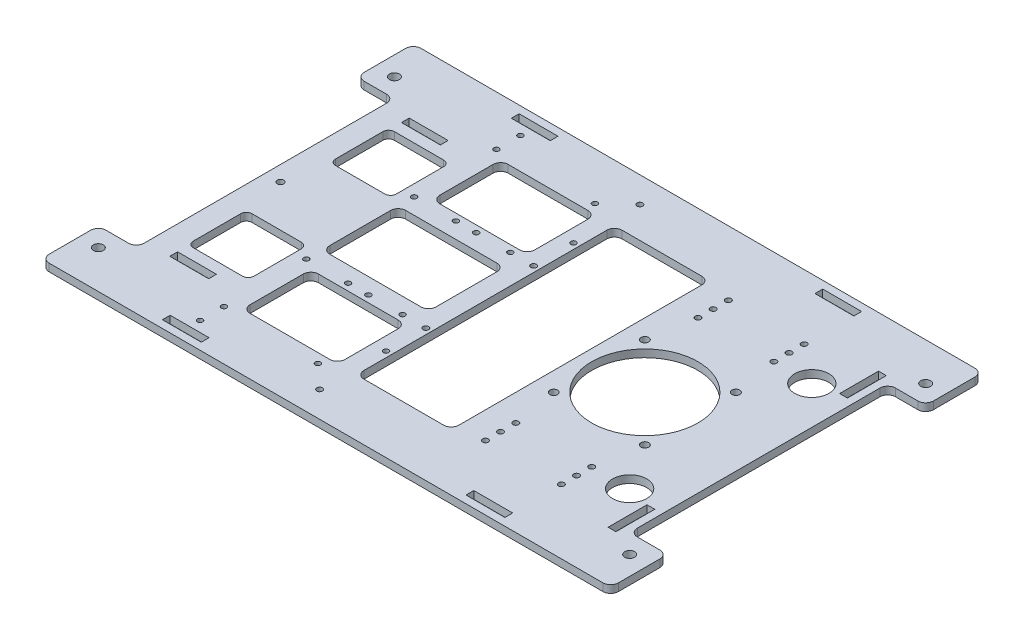
SolidWorks part; units mm, degrees
material "Ст 3 ГОСТ 380-88"
ref_plane "Спереди" through (0, 0, 0) normal (0, 0, 1) x (1, 0, 0)
ref_plane "Сверху" through (0, 0, 0) normal (0, 1, 0) x (1, 0, 0)
ref_plane "Справа" through (0, 0, 0) normal (1, 0, 0) x (0, 0, -1)
other "Configuration Table"
sketch "Эскиз1" plane through (0, 0, 0) normal (0, 1, 0) x (1, 0, 0)
  line L0 (0, -170.1085) -> (0, -191.8915)
  line L1 (4.1085, 0) -> (295.8915, 0)
  line L2 (0, -4.1085) -> (0, -25.8915)
  line L3 (4.1085, -196) -> (295.8915, -196)
  line L4 (300, -4.1085) -> (300, -25.8915)
  line L5 (4.1085, -30) -> (15.8915, -30)
  line L7 (4.1085, -166) -> (15.8915, -166)
  line L8 (20, -34.1085) -> (20, -161.8915)
  line L9 (295.8915, -30) -> (284.1085, -30)
  line L11 (295.8915, -166) -> (284.1085, -166)
  line L12 (280, -34.1085) -> (280, -161.8915)
  line L13 (300, -170.1085) -> (300, -191.8915)
  line L14 (-22.5077, -98) -> (393.8408, -98) construction
  circle A0 centre (220, -98) radius 28
  arc A1 (295.8915, -30) -> (300, -25.8915) centre (295.8915, -25.8915) ccw
  arc A2 (295.8915, 0) -> (300, -4.1085) centre (295.8915, -4.1085) cw
  arc A3 (284.1085, -30) -> (280, -34.1085) centre (284.1085, -34.1085) ccw
  arc A4 (284.1085, -166) -> (280, -161.8915) centre (284.1085, -161.8915) cw
  arc A5 (300, -170.1085) -> (295.8915, -166) centre (295.8915, -170.1085) ccw
  arc A6 (295.8915, -196) -> (300, -191.8915) centre (295.8915, -191.8915) ccw
  arc A7 (0, -191.8915) -> (4.1085, -196) centre (4.1085, -191.8915) ccw
  arc A8 (0, -170.1085) -> (4.1085, -166) centre (4.1085, -170.1085) cw
  arc A9 (15.8915, -166) -> (20, -161.8915) centre (15.8915, -161.8915) ccw
  arc A10 (15.8915, -30) -> (20, -34.1085) centre (15.8915, -34.1085) cw
  arc A11 (4.1085, -30) -> (0, -25.8915) centre (4.1085, -25.8915) cw
  arc A12 (4.1085, 0) -> (0, -4.1085) centre (4.1085, -4.1085) ccw
  circle A13 centre (10, -20) radius 2.6
  circle A14 centre (290, -20) radius 2.6
  circle A15 centre (290, -176) radius 2.6
  circle A16 centre (10, -176) radius 2.6
  point P19 (300, -30)
  point P22 (300, 0)
  point P25 (280, -30)
  point P34 (0, -196)
  point P41 (20, -30)
  point P44 (0, -30)
  point P47 (0, 0)
  dimension "D8" = 56
  dimension "D10" = 4.1085
  dimension "D11" = 5.2
  dimension "D12" = 5.2
  dimension "D1" = 300
  dimension "D2" = 196
  dimension "D3" = 20
  dimension "D4" = 30
  dimension "D5" = 30
  dimension "D6" = 20
  dimension "D7" = 98
  dimension "D9" = 60
  dimension "D13" = 10
  dimension "D14" = 10
  dimension "D15" = 10
  dimension "D16" = 10
base flange "Базовая кромка1" sketch "Эскиз1" thickness 4 reverse thickness direction no parameters "D1"=4
sketch "Эскиз6" plane through (0, 0, 0) normal (0, 1, 0) x (1, 0, 0)
  line L0 (0, -98) -> (316.488, -98) construction
  line L1 (271.9, -26.75) -> (276, -26.75)
  line L2 (271.9, -26.75) -> (271.9, -47.25)
  line L3 (271.9, -47.25) -> (276, -47.25)
  line L4 (276, -26.75) -> (276, -47.25)
  line L5 (219.75, -4) -> (240.25, -4)
  line L6 (219.75, -4) -> (219.75, -8.1)
  line L7 (219.75, -8.1) -> (240.25, -8.1)
  line L8 (240.25, -4) -> (240.25, -8.1)
  line L9 (59.75, -4) -> (80.25, -4)
  line L10 (59.75, -4) -> (59.75, -8.1)
  line L11 (59.75, -8.1) -> (80.25, -8.1)
  line L12 (80.25, -4) -> (80.25, -8.1)
  line L21 (295.8915, 0) -> (4.1085, 0) construction
  line L22 (280, -161.8915) -> (280, -34.1085) construction
  line L23 (20, -34.1085) -> (20, -161.8915) construction
  line L24 (32.75, -34.9) -> (53.25, -34.9)
  line L25 (32.75, -34.9) -> (32.75, -39)
  line L26 (32.75, -39) -> (53.25, -39)
  line L27 (53.25, -34.9) -> (53.25, -39)
  line L28 (53.25, -161.1) -> (53.25, -157)
  line L29 (32.75, -157) -> (53.25, -157)
  line L30 (32.75, -161.1) -> (32.75, -157)
  line L31 (32.75, -161.1) -> (53.25, -161.1)
  line L32 (80.25, -192) -> (80.25, -187.9)
  line L33 (59.75, -187.9) -> (80.25, -187.9)
  line L34 (59.75, -192) -> (59.75, -187.9)
  line L35 (59.75, -192) -> (80.25, -192)
  line L36 (240.25, -192) -> (240.25, -187.9)
  line L37 (219.75, -187.9) -> (240.25, -187.9)
  line L38 (219.75, -192) -> (219.75, -187.9)
  line L39 (219.75, -192) -> (240.25, -192)
  line L40 (276, -169.25) -> (276, -148.75)
  line L41 (271.9, -148.75) -> (276, -148.75)
  line L42 (271.9, -169.25) -> (271.9, -148.75)
  line L43 (271.9, -169.25) -> (276, -169.25)
  dimension "D1" = 98
  dimension "D2" = 20.5
  dimension "D3" = 20.5
  dimension "D4" = 20.5
  dimension "D5" = 4.1
  dimension "D6" = 4
  dimension "D7" = 4
  dimension "D8" = 4
  dimension "D9" = 20.5
  dimension "D10" = 4.1
  dimension "D11" = 39.75
  dimension "D12" = 39.75
  dimension "D13" = 35
  dimension "D14" = 12.75
  dimension "D15" = 26.75
extrude "Вырез-Вытянуть1" cut sketch "Эскиз6" against normal up to next normal cut yes
sketch "Эскиз7" plane through (0, 0, 0) normal (0, 1, 0) x (1, 0, 0)
  line L0 (4.1085, 0) -> (295.8915, 0) construction
  line L1 (140, -30) -> (182, -30)
  line L2 (136, -34) -> (136, -162)
  line L3 (140, -166) -> (182, -166)
  line L4 (186, -34) -> (186, -162)
  line L5 (4.1085, -196) -> (295.8915, -196) construction
  line L6 (280, -34.1085) -> (280, -161.8915) construction
  line L7 (20, -34.1085) -> (20, -161.8915) construction
  line L8 (74, -78) -> (122, -78)
  line L9 (70, -82) -> (70, -114)
  line L10 (74, -118) -> (122, -118)
  line L11 (126, -82) -> (126, -114)
  line L12 (-22.5077, -98) -> (393.8408, -98) construction
  line L14 (32.75, -39) -> (53.25, -39) construction
  line L15 (35, -45) -> (61, -45)
  line L16 (32, -48) -> (32, -73)
  line L17 (35, -76) -> (61, -76)
  line L18 (64, -48) -> (64, -73)
  line L19 (20, -34.1085) -> (20, -161.8915) construction
  line L20 (220, -98) -> (-41.1636, -98) construction
  line L21 (64, -148) -> (64, -123)
  line L22 (35, -120) -> (61, -120)
  line L23 (32, -148) -> (32, -123)
  line L24 (35, -151) -> (61, -151)
  arc A0 (136, -162) -> (140, -166) centre (140, -162) ccw
  arc A1 (182, -166) -> (186, -162) centre (182, -162) ccw
  arc A2 (182, -30) -> (186, -34) centre (182, -34) cw
  arc A3 (140, -30) -> (136, -34) centre (140, -34) ccw
  arc A4 (122, -78) -> (126, -82) centre (122, -82) cw
  arc A5 (122, -118) -> (126, -114) centre (122, -114) ccw
  arc A6 (70, -114) -> (74, -118) centre (74, -114) ccw
  arc A7 (74, -78) -> (70, -82) centre (74, -82) ccw
  circle A8 centre (196, -74) radius 2.05
  circle A9 centre (220, -98) radius 28 construction
  circle A10 centre (244, -74) radius 2.05
  circle A11 centre (244, -122) radius 2.05
  circle A12 centre (196, -122) radius 2.05
  arc A13 (61, -76) -> (64, -73) centre (61, -73) ccw
  arc A14 (61, -45) -> (64, -48) centre (61, -48) cw
  arc A15 (35, -45) -> (32, -48) centre (35, -48) ccw
  arc A16 (32, -73) -> (35, -76) centre (35, -73) ccw
  arc A17 (32, -123) -> (35, -120) centre (35, -123) cw
  arc A18 (35, -151) -> (32, -148) centre (35, -148) cw
  arc A19 (61, -151) -> (64, -148) centre (61, -148) ccw
  arc A20 (61, -120) -> (64, -123) centre (61, -123) cw
  point P24 (186, -30)
  point P27 (136, -30)
  point P61 (64, -45)
  point P64 (32, -45)
  point P79 (32, -151)
  point P80 (64, -151)
  dimension "D9" = 4
  dimension "D12" = 4.1
  dimension "D18" = 3
  dimension "D1" = 30
  dimension "D2" = 30
  dimension "D3" = 94
  dimension "D4" = 50
  dimension "D5" = 50
  dimension "D6" = 40
  dimension "D7" = 20
  dimension "D8" = 10
  dimension "D10" = 24
  dimension "D11" = 24
  dimension "D14" = 22
  dimension "D15" = 6
  dimension "D16" = 12
  dimension "D17" = 32
  dimension "D13" = 2
extrude "Вырез-Вытянуть2" cut sketch "Эскиз7" against normal up to next normal cut yes
sketch "Эскиз14" plane through (0, 0, 0) normal (0, 1, 0) x (1, 0, 0)
  line L0 (295.8915, 0) -> (4.1085, 0) construction
  line L2 (0, -98) -> (328.8146, -98) construction
  line L5 (20, -34.1085) -> (20, -161.8915) construction
  line L6 (122, -78) -> (74, -78) construction
  line L7 (80, -30) -> (122, -30)
  line L8 (76, -34) -> (76, -62)
  line L9 (80, -66) -> (122, -66)
  line L10 (126, -34) -> (126, -62)
  line L11 (136, -34) -> (136, -162) construction
  line L12 (126, -162) -> (126, -134)
  line L13 (80, -130) -> (122, -130)
  line L14 (76, -162) -> (76, -134)
  line L15 (80, -166) -> (122, -166)
  circle A0 centre (70, -26.2) radius 1.4
  circle A1 centre (120.7, -25) radius 1.4
  circle A2 centre (70, -69.6) radius 1.4
  circle A3 centre (120.7, -69.6) radius 1.4
  circle A4 centre (70, -13.6) radius 1.4
  circle A5 centre (133, -13.6) radius 1.4947
  circle A6 centre (133, -69.6) radius 1.4762
  circle A7 centre (133, -126.4) radius 1.4762
  circle A8 centre (133, -182.4) radius 1.4947
  circle A9 centre (70, -182.4) radius 1.4
  circle A10 centre (120.7, -126.4) radius 1.4
  circle A11 centre (70, -126.4) radius 1.4
  circle A12 centre (120.7, -171) radius 1.4
  circle A13 centre (70, -169.8) radius 1.4
  arc A14 (122, -30) -> (126, -34) centre (122, -34) cw
  arc A15 (122, -66) -> (126, -62) centre (122, -62) ccw
  arc A16 (76, -62) -> (80, -66) centre (80, -62) ccw
  arc A17 (80, -30) -> (76, -34) centre (80, -34) ccw
  arc A18 (80, -166) -> (76, -162) centre (80, -162) cw
  arc A19 (76, -134) -> (80, -130) centre (80, -134) cw
  arc A20 (122, -130) -> (126, -134) centre (122, -134) cw
  arc A21 (122, -166) -> (126, -162) centre (122, -162) ccw
  circle A22 centre (133, -48.6) radius 1.4
  circle A23 centre (92, -69.6) radius 1.4
  circle A24 centre (61.7, -48.6) radius 1.4
  circle A25 centre (102.7, -69.6) radius 1.4
  circle A26 centre (102.7, -126.4) radius 1.4
  circle A27 centre (92, -126.4) radius 1.4
  circle A28 centre (133, -147.4) radius 1.4
  circle A29 centre (61.7, -147.4) radius 1.4
  circle A30 centre (28, -98) radius 1.75
  point P46 (126, -66)
  point P49 (76, -66)
  point P64 (76, -130)
  point P65 (126, -130)
  dimension "D2" = 2.8
  dimension "D14" = 4
  dimension "D21" = 3.5
  dimension "D1" = 50.7
  dimension "D3" = 43.4
  dimension "D4" = 44.6
  dimension "D5" = 25
  dimension "D6" = 50
  dimension "D7" = 98
  dimension "D8" = 56
  dimension "D9" = 63
  dimension "D10" = 50
  dimension "D11" = 30
  dimension "D12" = 12
  dimension "D13" = 10
  dimension "D15" = 21
  dimension "D16" = 41
  dimension "D17" = 21
  dimension "D18" = 41
  dimension "D19" = 18
  dimension "D20" = 8
extrude "Вырез-Вытянуть3" cut sketch "Эскиз14" against normal through all normal cut yes
sketch "Эскиз15" plane through (0, 0, 0) normal (0, 1, 0) x (1, 0, 0)
  line L0 (295.8915, 0) -> (4.1085, 0) construction
  line L1 (300, -25.8915) -> (300, -4.1085) construction
  line L2 (248, -98) -> (358.3996, -98) construction
  line L3 (280, -161.8915) -> (280, -34.1085) construction
  circle A0 centre (200, -34) radius 1.5
  circle A1 centre (240, -34) radius 1.5
  circle A2 centre (240, -42) radius 1.5
  circle A3 centre (240, -50) radius 1.5
  circle A4 centre (200, -42) radius 1.5
  circle A5 centre (200, -50) radius 1.5
  circle A6 centre (220, -98) radius 28 construction
  circle A7 centre (200, -146) radius 1.5
  circle A8 centre (200, -154) radius 1.5
  circle A9 centre (240, -146) radius 1.5
  circle A10 centre (240, -154) radius 1.5
  circle A11 centre (240, -162) radius 1.5
  circle A12 centre (200, -162) radius 1.5
  circle A13 centre (260, -50) radius 9
  circle A14 centre (260, -146) radius 9
  dimension "D3" = 3
  dimension "D4" = 3
  dimension "D6" = 18
  dimension "D1" = 34
  dimension "D2" = 100
  dimension "D7" = 20
  dimension "D8" = 50
  dimension "D5" = 2
extrude "Вырез-Вытянуть4" cut sketch "Эскиз15" against normal through all normal cut yes
sketch "Сгиб-Линии1" [suppressed] plane through (0, 0, 0) normal (0, 1, 0) x (1, 0, 0)
sketch "Граничная рамка1" [suppressed] plane through (0, 0, 0) normal (0, 1, 0) x (1, 0, 0)
sheet metal parameters "Листовой металл3" thickness 4 parameters "D1"=4
flat pattern "Развертка3" [suppressed]
sketch "Сгиб-Линии2" plane through (0, 0, 0) normal (0, 1, 0) x (1, 0, 0)
sketch "Граничная рамка2" [suppressed] plane through (0, 0, 0) normal (0, 1, 0) x (1, 0, 0)
sheet metal parameters "Листовой металл4" thickness 4 parameters "D1"=4
flat pattern "Развертка3"
sketch "Сгиб-Линии2" plane through (0, 0, 0) normal (0, 1, 0) x (1, 0, 0)
sketch "Граничная рамка2" [suppressed] plane through (0, 0, 0) normal (0, 1, 0) x (1, 0, 0)
sheet metal parameters "Листовой металл5" thickness 4 parameters "D1"=4
flat pattern "Развертка3"
sketch "Сгиб-Линии2" plane through (0, 0, 0) normal (0, 1, 0) x (1, 0, 0)
sketch "Граничная рамка2" [suppressed] plane through (0, 0, 0) normal (0, 1, 0) x (1, 0, 0)
sheet metal parameters "Листовой металл6" thickness 4 parameters "D1"=4
flat pattern "Развертка6"
sketch "Сгиб-Линии3" plane through (0, 0, 0) normal (0, 1, 0) x (1, 0, 0)
sketch "Граничная рамка3" [suppressed] plane through (0, 0, 0) normal (0, 1, 0) x (1, 0, 0)
sheet metal parameters "Листовой металл7" thickness 4 parameters "D1"=4
flat pattern "Развертка7"
sketch "Сгиб-Линии4" plane through (0, 0, 0) normal (0, 1, 0) x (1, 0, 0)
sketch "Граничная рамка4" [suppressed] plane through (0, 0, 0) normal (0, 1, 0) x (1, 0, 0)
sheet metal parameters "Листовой металл8" thickness 4 parameters "D1"=4
flat pattern "Развертка3"
sketch "Сгиб-Линии2" plane through (0, 0, 0) normal (0, 1, 0) x (1, 0, 0)
sketch "Граничная рамка2" [suppressed] plane through (0, 0, 0) normal (0, 1, 0) x (1, 0, 0)
sheet metal parameters "Листовой металл9" thickness 4 parameters "D1"=4
flat pattern "Развертка3"
sketch "Сгиб-Линии2" plane through (0, 0, 0) normal (0, 1, 0) x (1, 0, 0)
sketch3d "Граничная рамка2" [suppressed]
  line L0 (-295.8915, -170.1084, 0) -> (4.1085, -170.1085, 0) construction
  line L1 (-295.8915, 25.8915, 0) -> (4.1085, 25.8915, 0) construction
  line L2 (-295.8915, -170.1084, 0) -> (-295.8915, 25.8915, 0) construction
  line L3 (4.1085, -170.1085, 0) -> (4.1085, 25.8915, 0) construction
